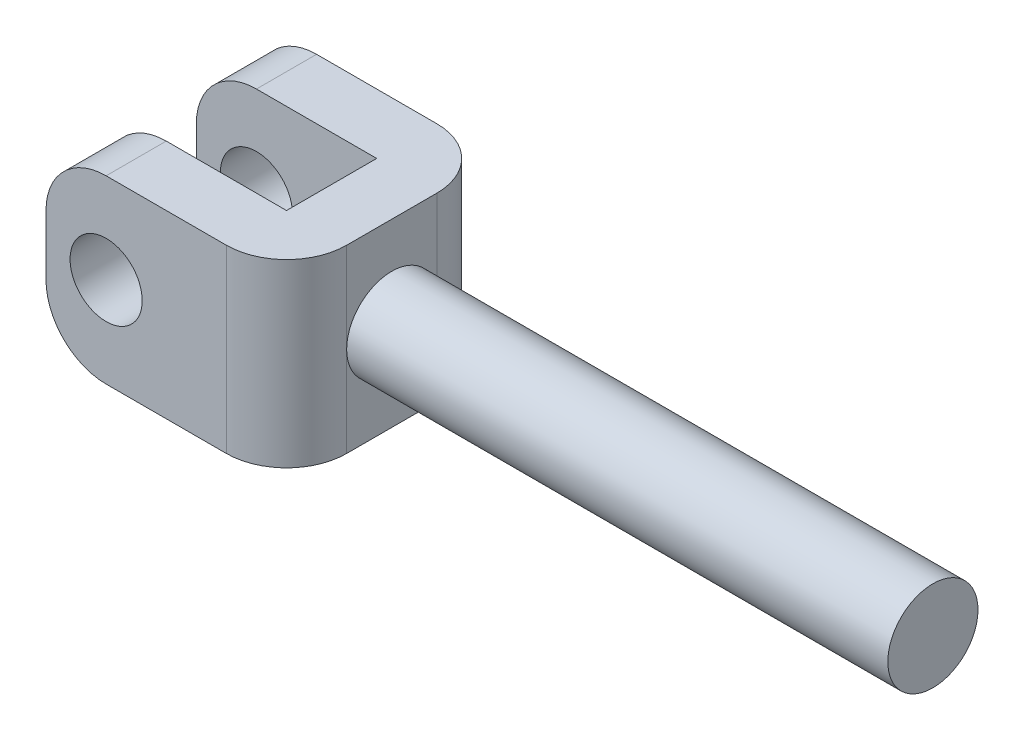
SolidWorks part; units mm, degrees
ref_plane "Front Plane" through (0, 0, 0) normal (0, 0, 1) x (1, 0, 0)
ref_plane "Top Plane" through (0, 0, 0) normal (0, 1, 0) x (1, 0, 0)
ref_plane "Right Plane" through (0, 0, 0) normal (1, 0, 0) x (0, 0, -1)
sketch "Sketch1" plane through (0, 0, 0) normal (1, 0, 0) x (0, 0, -1)
  circle A0 centre (0, 0) radius 0.75
  dimension "D1" = 1.5
extrude "Boss-Extrude1" add sketch "Sketch1" along normal blind 10
sketch "Sketch2" plane through (0, 0, 0) normal (0, 1, 0) x (1, 0, 0)
  line L0 (1, 1.75) -> (1, -1.75)
  line L2 (0, 0.75) -> (0, -0.75)
  line L5 (1, -1.75) -> (-3, -1.75)
  line L6 (-3, 1.75) -> (-3, 0.75)
  line L7 (1, 1.75) -> (-3, 1.75)
  line L8 (0, 0.75) -> (-3, 0.75)
  line L10 (-3, -0.75) -> (0, -0.75)
  line L11 (-3, -0.75) -> (-3, -1.75)
  line L13 (-3, 1.75) -> (-3, -1.75) construction
  line L14 (-2, 0.75) -> (-2, -0.75) construction
  line L15 (0, 0.75) -> (-2, 0.75) construction
  line L16 (0, -0.75) -> (-2, -0.75) construction
  dimension "D1" = 4
  dimension "D2" = 1
extrude "Boss-Extrude2" add sketch "Sketch2" along normal blind 1.5 and the other way blind 1.5
fillet "Fillet1" radius 1 6 edges at (-3, 1.5, -1.25) (-3, -1.5, -1.25) (-3, -1.5, 1.25) (-3, 1.5, 1.25) (1, 0, -1.75) (1, 0, 1.75)
sketch "Sketch3" plane through (0, 0, -1.75) normal (0, 0, -1) x (-1, 0, 0)
  line L0 (0, -1.5) -> (2, -1.5) construction
  line L2 (0, 1.5) -> (0, -1.5) construction
  circle A0 centre (2, 0) radius 0.6
  dimension "D1" = 1.2
  dimension "D2" = 1.5
  dimension "D3" = 2
extrude "Cut-Extrude1" cut sketch "Sketch3" against normal blind 5
